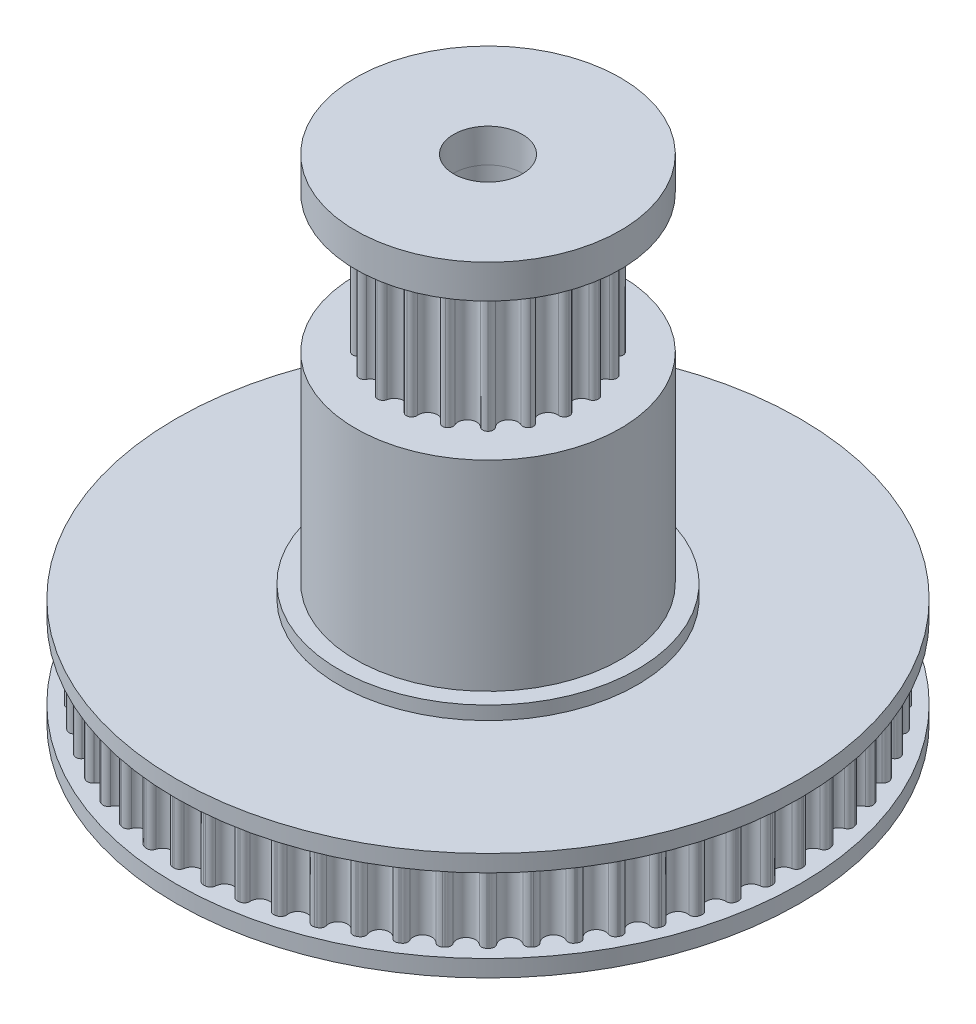
SolidWorks part; units mm, degrees
ref_plane "Front Plane" through (0, 0, 0) normal (0, 0, 1) x (1, 0, 0)
ref_plane "Top Plane" through (0, 0, 0) normal (0, 1, 0) x (1, 0, 0)
ref_plane "Right Plane" through (0, 0, 0) normal (1, 0, 0) x (0, 0, -1)
sketch "PulleyOffsets" plane through (0, 0, 0) normal (1, 0, 0) x (0, 0, -1)
  line L0 (15.875, 0) -> (-15.875, 0) construction
  line L1 (15.875, 31.75) -> (-15.875, 31.75) construction
  line L2 (0, 0) -> (0, 31.75) construction
  point P7 (0, 0)
  dimension "D1" = 31.75
ref_axis "Axis1" through (0, 34.9332, 0) along (0, -1, 0)
ref_plane "Big Pulley Plane" through (0, 0, 0) normal (0, 1, 0) x (1, 0, 0)
ref_plane "Small Pulley Plane" through (0, 31.75, 0) normal (0, 1, 0) x (1, 0, 0)
sketch "Sketch1" plane through (0, 0, 0) normal (0, 1, 0) x (1, 0, 0)
  line L0 (0, 0) -> (0, 28.2667) construction
  line L1 (0, 0) -> (2.9202, 27.7837) construction
  circle A0 centre (0, 0) radius 28.2667 construction
  circle A1 centre (0, 0) radius 27.0467 construction
  circle A2 centre (0, 27.9367) radius 0.89 construction
  circle A5 centre (2.9202, 27.7837) radius 0.89 construction
  arc A6 (0, 27.0467) -> (0.8804, 27.8061) centre (0, 27.9367) ccw
  arc A7 (0.8804, 27.8061) -> (1.3997, 28.2321) centre (1.3749, 27.7327) cw
  arc A8 (1.559, 28.2237) -> (2.031, 27.7458) centre (1.5314, 27.7245) cw
  arc A9 (2.8272, 26.8986) -> (2.031, 27.7458) centre (2.9202, 27.7837) cw
  arc A10 (1.3997, 28.2321) -> (1.559, 28.2237) centre (0, 0) cw
  arc A11 (0, 27.0467) -> (2.8272, 26.8986) centre (0, 0) ccw
  dimension "D1" = 56.5335
  dimension "D3" = 1.78
  dimension "D4" = 0.5
  dimension "D2" = 1.22
  dimension "D5" = 6
extrude "Boss-Extrude1" add sketch "Sketch1" along normal mid plane 7.112 contours A6 A11 A9 A8 A7 region at (0.001, 0, -0.0192)
pattern_circular "CirPattern1" count 60 over 360 about axis through (0, 34.9332, 0) along (0, -1, 0) of "Boss-Extrude1"
sketch "Sketch2" plane through (0, 0, 0) normal (1, 0, 0) x (0, 0, -1)
  line L10 (0, 3.5) -> (29.4415, 3.5) construction
  line L11 (0, 3.5) -> (0, 5.0875) construction
  line L12 (0, 5.0875) -> (29.4415, 5.0875) construction
  line L15 (29.4415, 3.5) -> (29.4415, 5.0875) construction
  line L20 (0, 34.9332) -> (0, -6.9932) construction
  line L22 (29.4415, 5.0875) -> (0, 5.0875)
  line L23 (29.4415, 5.0875) -> (29.4415, 3.5)
  line L24 (29.4415, 3.5) -> (0, 3.5)
  line L25 (0, 5.0875) -> (0, 3.5)
  dimension "D1" = 1.5875
  dimension "D2" = 29.4415
  dimension "D3" = 3.5
revolve "Revolve3" add sketch "Sketch2" angle 360 about axis through (0, 34.9332, 0) along (0, -1, 0) region at (0, 4.2937, -14.7207)
mirror "Mirror1" about plane through (0, 0, 0) normal (0, 1, 0) of "Revolve3"
sketch "Sketch3" plane through (0, 0, 0) normal (0, 1, 0) x (1, 0, 0)
  circle A0 centre (0, 0) radius 22.225
  dimension "D1" = 44.45
extrude "Cut-Extrude1" [suppressed] cut sketch "Sketch3" against normal through all both and the other way through all
sketch "Sketch6" plane through (0, 0, 0) normal (0, 1, 0) x (1, 0, 0)
  line L0 (0, 0) -> (0, 9.1676) construction
  line L1 (0, 0) -> (2.731, 8.405) construction
  circle A0 centre (0, 0) radius 9.1676 construction
  circle A1 centre (0, 0) radius 7.9476 construction
  circle A2 centre (0, 8.8376) radius 0.89 construction
  circle A5 centre (2.731, 8.405) radius 0.89 construction
  arc A6 (0, 7.9476) -> (0.8721, 8.6598) centre (0, 8.8376) ccw
  arc A7 (0.8721, 8.6598) -> (1.4405, 9.0537) centre (1.362, 8.5599) cw
  arc A8 (1.4277, 9.0557) -> (1.8466, 8.5054) centre (1.3498, 8.5618) cw
  arc A9 (2.4559, 7.5586) -> (1.8466, 8.5054) centre (2.731, 8.405) cw
  arc A10 (1.4405, 9.0537) -> (1.4277, 9.0557) centre (0, 0) cw construction
  arc A11 (0, 7.9476) -> (2.4559, 7.5586) centre (0, 0) ccw
  arc A12 (1.4405, 9.0537) -> (1.4277, 9.0557) centre (0, 0) cw
  dimension "D3" = 1.78
  dimension "D4" = 0.5
  dimension "D2" = 1.22
  dimension "D1" = 18.3352
  dimension "D5" = 18
extrude "Boss-Extrude2" add sketch "Sketch6" along normal mid plane 13 from surface contours A6 A11 A9 A8 A7 region at (0.0089, 0, -0.0564) starting at plane "Small Pulley Plane"
pattern_circular "CirPattern2" count 20 over 360 about axis through (0, 34.9332, 0) along (0, -1, 0) of "Boss-Extrude2"
sketch "Sketch4" plane through (0, 0, 0) normal (0, 0, 1) x (1, 0, 0)
  line L0 (14.0875, 5.0875) -> (-14.0875, 5.0875) construction
  line L1 (29.4415, 5.0875) -> (-29.4415, 5.0875) construction
  line L2 (-14.0875, 5.0875) -> (-14.0875, 6.3575)
  line L3 (-14.0875, 6.3575) -> (-12.5, 6.3575)
  line L4 (-12.5, 6.3575) -> (-12.5, 25.25)
  line L5 (0, 0) -> (0, 41.425) construction
  line L6 (12.5, 6.3575) -> (12.5, 25.25) construction
  line L7 (14.0875, 6.3575) -> (12.5, 6.3575) construction
  line L8 (14.0875, 5.0875) -> (14.0875, 6.3575) construction
  line L9 (-12.5, 25.25) -> (12.5, 25.25) construction
  line L10 (-14.0875, 5.0875) -> (0, 5.0875)
  line L11 (0, 5.0875) -> (0, 25.25)
  line L12 (0, 25.25) -> (-12.5, 25.25)
  line L13 (1.841, 25.25) -> (3.5054, 25.25) construction
  line L14 (0.8721, 38.25) -> (-0.8721, 38.25) construction
  line L15 (-12.5, 41.425) -> (0, 41.425)
  line L16 (-12.5, 41.425) -> (-12.5, 38.25)
  line L17 (-12.5, 38.25) -> (0, 38.25)
  line L18 (0, 41.425) -> (0, 38.25)
  line L19 (-12.5, 25.25) -> (-12.5, 38.25) construction
  point P14 (0, 5.0875)
  dimension "D1" = 1.27
  dimension "D2" = 1.5875
  dimension "D3" = 25
  dimension "D4" = 3.175
revolve "Revolve4" add sketch "Sketch4" angle 360 about L11
sketch "Sketch7" plane through (0, 41.425, 0) normal (0, 1, 0) x (1, 0, 0)
  circle A0 centre (0, 0) radius 3.2385
  dimension "D1" = 6.477
extrude "Cut-Extrude2" cut sketch "Sketch7" against normal through all both and the other way through all
sketch "Sketch8" plane through (0, -5.0875, 0) normal (0, -1, 0) x (1, 0, 0)
  circle A0 centre (0, 0) radius 4.7625
  dimension "D1" = 9.525
equation "\"TEETH_NUM\"= 60"
equation "\"TOOTH_PITCH\"= 3mm"
equation "\"PITCH_LINE_OFFSET\"= .015in"
equation "\"DIAMETER_PER_GROOVE\"= \"OUTSIDE_DIAMETER\" / \"TEETH_NUM\" * 1in"
equation "\"PITCH_DIAMETER\"= ( ( \"TEETH_NUM\" * 3 - 1.31 ) / 3.1415 + .415 ) * 1mm"
equation "\"OUTSIDE_DIAMETER\"= \"PITCH_DIAMETER\" - \"PITCH_LINE_OFFSET\" * 2"
equation "\"D1@Sketch1\"=\"OUTSIDE_DIAMETER\""
equation "\"TOOTH_HEIGHT\"= 1.22mm"
equation "\"D2@Sketch1\"=\"TOOTH_HEIGHT\""
equation "\"TOOTH_DIAMETER\"= 1.78mm"
equation "\"INTERNAL_RADIUS\"= .5mm"
equation "\"D3@Sketch1\"=\"TOOTH_DIAMETER\""
equation "\"D5@Sketch1\"=360 / \"TEETH_NUM\""
equation "\"D4@Sketch1\"=\"INTERNAL_RADIUS\""
equation "\"D1@CirPattern1\"=\"TEETH_NUM\""
equation "\"BELT_GAP\"= 7mm"
equation "\"D2@Sketch2\"=\"PITCH_DIAMETER\"/2+1/32"
equation "\"D3@Sketch2\"=\"BELT_GAP\"/2"
equation "\"2_TEETH_NUM\"= 20"
equation "\"2_PITCH_DIAMETER\"= ( ( \"2_TEETH_NUM\" * 3 - 1.31 ) / 3.1415 + .415 ) * 1mm"
equation "\"2_OUTSIDE_DIAMETER\"= \"2_PITCH_DIAMETER\" - \"PITCH_LINE_OFFSET\" * 2"
equation "\"2_DIAMETER_PER_GROOVE\"= \"2_OUTSIDE_DIAMETER\" / \"2_TEETH_NUM\" * 1in"
equation "\"D5@Sketch6\"=360/\"2_TEETH_NUM\""
equation "\"D1@Sketch6\"=\"2_OUTSIDE_DIAMETER\""
equation "\"D2@Sketch6\"=\"TOOTH_HEIGHT\""
equation "\"D3@Sketch6\"=\"TOOTH_DIAMETER\""
equation "\"D4@Sketch6\"=\"INTERNAL_RADIUS\""
equation "\"2_BELT_GAP\"= 13mm"
equation "\"D1@CirPattern2\"=\"2_TEETH_NUM\""
equation "\"D1@Boss-Extrude2\"=\"2_BELT_GAP\""
equation "\"Pulley_OffSets\"= 1.25"
equation "\"D1@PulleyOffsets\" = \"Pulley_OffSets\""
